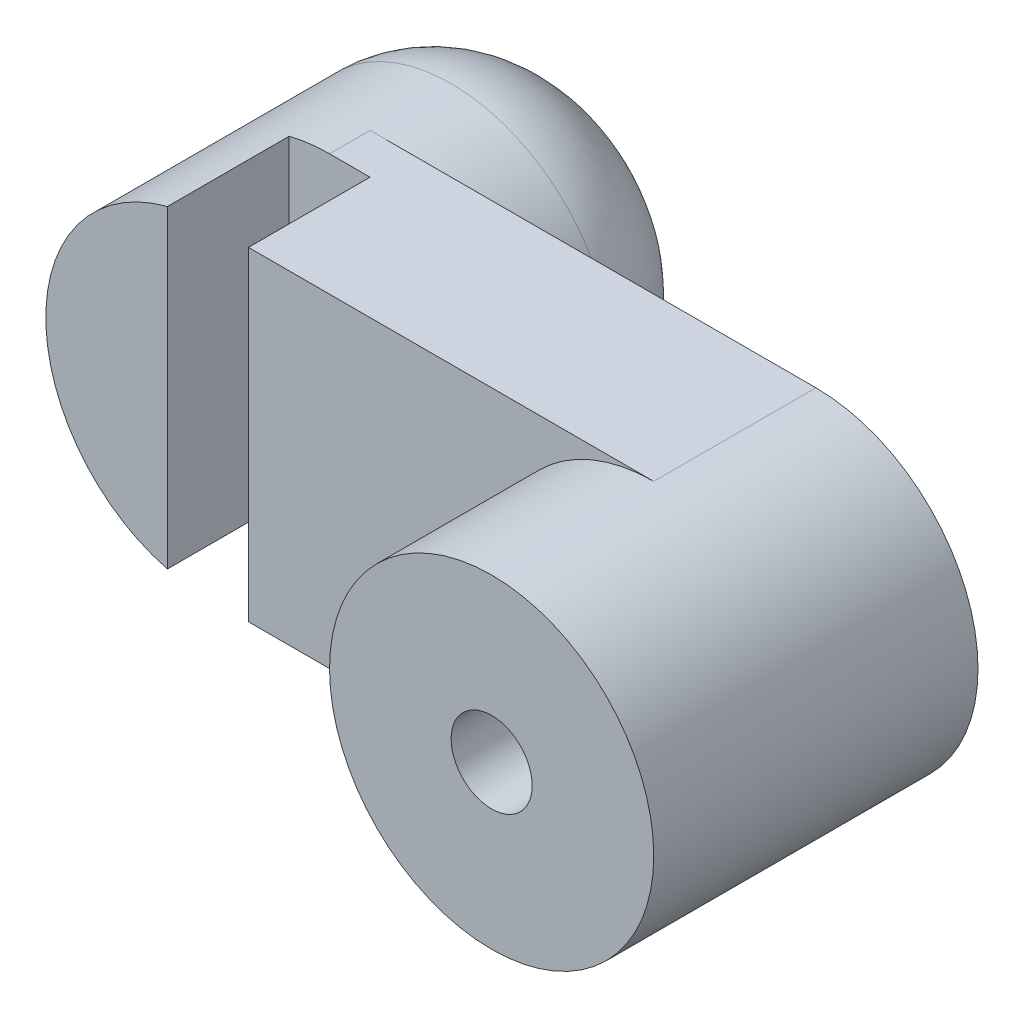
SolidWorks part; units mm, degrees
ref_plane "前视基准面" through (0, 0, 0) normal (0, 0, 1) x (1, 0, 0)
ref_plane "上视基准面" through (0, 0, 0) normal (0, 1, 0) x (1, 0, 0)
ref_plane "右视基准面" through (0, 0, 0) normal (1, 0, 0) x (0, 0, -1)
other "Configuration Table"
sketch "草图1" plane through (0, 0, 0) normal (0, 0, 1) x (1, 0, 0)
  circle A0 centre (0, 0) radius 2
  circle A1 centre (0, 0) radius 0.5
  dimension "D1" = 4
  dimension "D2" = 1
extrude "凸台-拉伸1" add sketch "草图1" along normal blind 4.5
fillet "圆角2" radius 1.5 1 edges at (2, 0, 0)
sketch "草图3" plane through (0, 0, 0) normal (0, 1, 0) x (1, 0, 0)
  line L0 (0, 0) -> (0, -2.5) construction
  line L1 (0, -2.5) -> (0, -4.5)
  line L2 (0, -2.5) -> (5.5, -2.5)
  line L3 (5.5, -2.5) -> (5.5, -4.5)
  line L4 (0, -4.5) -> (5.5, -4.5)
  dimension "D1" = 2.5
  dimension "D2" = 2
  dimension "D3" = 5.5
  dimension "D4" = 2
extrude "凸台-拉伸2" add sketch "草图3" along normal mid plane 4
sketch "草图4" plane through (0, 0, 2.5) normal (0, 0, -1) x (-1, 0, 0)
  line L0 (-5.5, 2) -> (-5.5, -2) construction
  circle A0 centre (-5.5, 0) radius 2
  circle A1 centre (-5.5, 0) radius 0.5
  dimension "D1" = 1
extrude "凸台-拉伸3" add sketch "草图4" against normal blind 2
sketch "草图5" plane through (0, 0, 2.5) normal (0, 0, -1) x (-1, 0, 0)
  line L0 (-5.5, 0.5) -> (-5.5, -0.5) construction
  circle A0 centre (-5.5, 0) radius 0.5
  dimension "D1" = 1
extrude "切除-拉伸2" cut sketch "草图5" against normal blind 4
sketch "草图6" plane through (0, 0, 4.5) normal (0, 0, 1) x (1, 0, 0)
  circle A0 centre (0, 0) radius 0.5
  dimension "D1" = 1
extrude "切除-拉伸3" cut sketch "草图6" against normal through all
sketch "草图2" plane through (0, 0, 4.5) normal (0, 0, 1) x (1, 0, 0)
  line L1 (-0.5, -2.0824) -> (0.5, -2.0824)
  line L2 (-0.5, -2.0824) -> (-0.5, 2.0824)
  line L3 (-0.5, 2.0824) -> (0.5, 2.0824)
  line L4 (0.5, -2.0824) -> (0.5, 2.0824)
  line L5 (-0.5, -2.0824) -> (0.5, 2.0824) construction
  line L6 (-0.5, 2.0824) -> (0.5, -2.0824) construction
  point P0 (0, 0)
  dimension "D1" = 1
extrude "切除-拉伸1" cut sketch "草图2" against normal blind 1.5
sketch "草图7" plane through (0, 0, 4.5) normal (0, 0, 1) x (1, 0, 0)
  circle A0 centre (5.5, 0) radius 0.5
  circle A1 centre (5.5, 0) radius 2
extrude "凸台-拉伸4" add sketch "草图7" along normal blind 2
